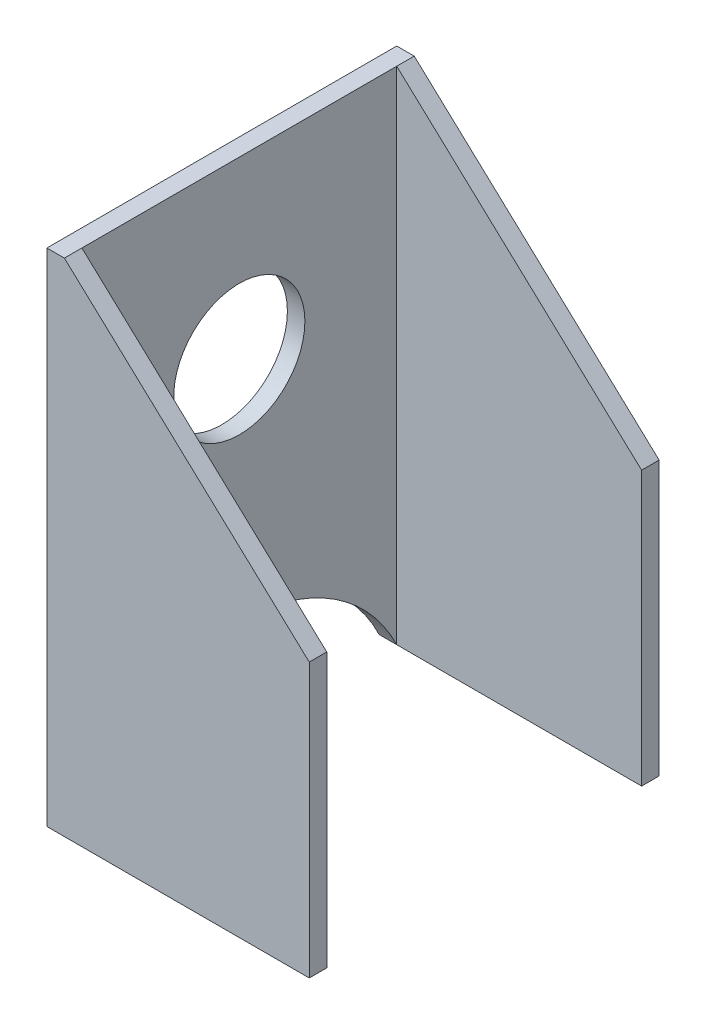
SolidWorks part; units mm, degrees
ref_plane "Front Plane" through (0, 0, 0) normal (0, 0, 1) x (1, 0, 0)
ref_plane "Top Plane" through (0, 0, 0) normal (0, 1, 0) x (1, 0, 0)
ref_plane "Right Plane" through (0, 0, 0) normal (1, 0, 0) x (0, 0, -1)
sketch "Sketch1" plane through (0, 0, 0) normal (1, 0, 0) x (0, 0, -1)
  line L0 (-11.43, 20.955) -> (-11.43, -15.4192)
  line L2 (-12.7, -20.955) -> (-12.7, 20.955)
  line L3 (-12.7, 20.955) -> (12.7, 20.955)
  line L4 (12.7, -20.955) -> (12.7, 20.955)
  line L5 (-12.7, -20.955) -> (12.7, 20.955) construction
  line L6 (-12.7, 20.955) -> (12.7, -20.955) construction
  line L7 (-11.43, -15.4192) -> (-12.7, -15.4192)
  line L8 (11.43, 20.955) -> (11.43, -15.4192)
  line L9 (11.43, -15.4192) -> (12.7, -15.4192)
  arc A0 (12.7, -20.955) -> (-12.7, -20.955) centre (0, -20.955) ccw
  circle A2 centre (0, 8.255) radius 4.7625
  point P0 (0, 0)
  dimension "D2" = 16.51
  dimension "D4" = 9.525
  dimension "D1" = 25.4
  dimension "D3" = 12.7
  dimension "D5" = 1.27
  dimension "D6" = 1.27
extrude "Boss-Extrude1" add sketch "Sketch1" along normal blind 1.27 contours A0 L8 L3 L0 A2 region at (0, 20.5254, 0)
extrude "Boss-Extrude2" add sketch "Sketch1<3>" along normal blind 19.05 contours L7 L0 L3 L2 | L8 L9 L4 L3 region at (0, 2.7679, 12.065) region at (0, 2.7679, -12.065)
sketch "Sketch1<3>" plane through (0, 0, 0) normal (1, 0, 0) x (0, 0, -1) same geometry as "Sketch1"
sketch "Sketch2" plane through (0, 0, 12.7) normal (0, 0, 1) x (1, 0, 0)
  line L0 (1.27, 20.955) -> (19.05, 4.445)
  line L1 (19.05, 20.955) -> (0, 20.955) construction
  line L2 (19.05, -15.4192) -> (19.05, 20.955) construction
  line L3 (19.05, 4.445) -> (19.05, 20.955)
  line L4 (19.05, 20.955) -> (1.27, 20.955)
  line L5 (0, -15.4192) -> (0, 20.955) construction
  dimension "D1" = 1.27
  dimension "D2" = 16.51
extrude "Cut-Extrude1" cut sketch "Sketch2" against normal blind 33.02
